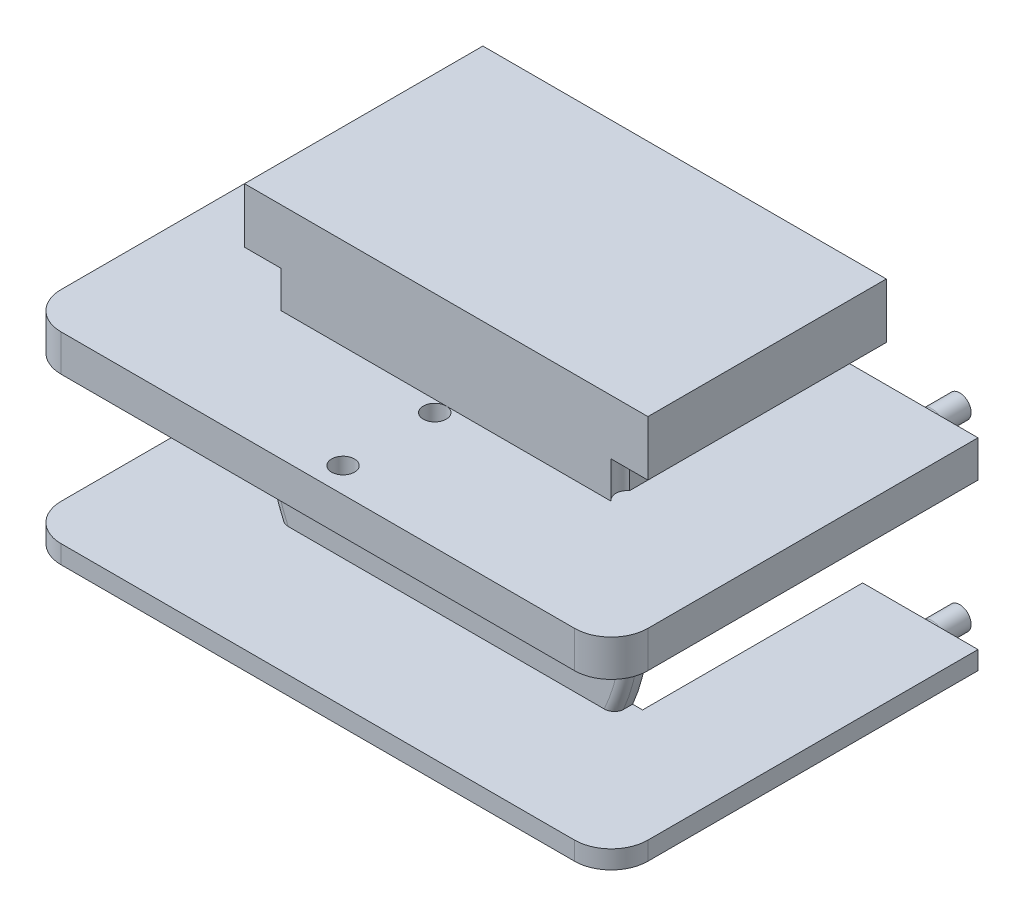
SolidWorks part; units mm, degrees
material "UNOBTANIUM"
ref_plane "Top Plane" through (0, 0, 0) normal (0, 0, 1) x (1, 0, 0)
ref_plane "Right Plane" through (0, 0, 0) normal (0, 1, 0) x (1, 0, 0)
ref_plane "Front Plane" through (0, 0, 0) normal (1, 0, 0) x (0, 0, -1)
ref_axis "x-axis" through (-17.6, 0, 0) along (1, 0, 0)
ref_axis "y-axis" through (0, -9.7375, 0) along (0, 1, 0)
ref_axis "z-axis" through (0, 0, 8.775) along (0, 0, -1)
sketch "Sketch1" plane through (0, 0, 0) normal (0, 0, 1) x (1, 0, 0)
  line L0 (-11, 6) -> (-11, 11)
  line L1 (-11, -6) -> (11, -6)
  line L2 (-11, -6) -> (-11, 6)
  line L3 (-11, 6) -> (11, 6) construction
  line L4 (11, -6) -> (11, 6)
  line L5 (-11, -6) -> (11, 6) construction
  line L6 (-11, 6) -> (11, -6) construction
  line L7 (-11, 11) -> (11, 11)
  line L8 (11, 11) -> (11, 6)
  circle A0 centre (0, 0) radius 9.25 construction
  point P0 (0, 0)
  dimension "D1" = 18.5
  dimension "D2" = 22
  dimension "D3" = 12
  dimension "D4" = 5
extrude "Boss-Extrude1" add sketch "Sketch1" along normal blind 1
sketch "Sketch2" plane through (0, 0, 0) normal (0, 0, -1) x (-1, 0, 0)
  circle A0 centre (0, 0) radius 1.475
  dimension "D1" = 2.95
extrude "Boss-Extrude2" add sketch "Sketch2" along normal blind 14
sketch "Sketch3" plane through (0, 0, 0) normal (0, 0, -1) x (-1, 0, 0)
  line L0 (11, -6) -> (-11, 6) construction
  circle A0 centre (0, 0) radius 1.8
  dimension "D1" = 3.6
extrude "Boss-Extrude3" add sketch "Sketch3" along normal blind 1
sketch "Sketch4" plane through (0, 0, 0) normal (0, 0, -1) x (-1, 0, 0)
  line L0 (11, -6) -> (-11, -6) construction
  line L1 (11, 11) -> (9, 11)
  line L2 (11, 11) -> (11, -6)
  line L3 (11, -6) -> (9, -6)
  line L4 (9, 11) -> (9, -6)
  line L5 (0, -6) -> (0, 11) construction
  line L7 (-9, 11) -> (-9, -6)
  line L8 (-11, -6) -> (-9, -6)
  line L9 (-11, 11) -> (-11, -6)
  line L10 (-11, 11) -> (-9, 11)
  line L11 (11, 11) -> (-11, 11) construction
  dimension "D1" = 2
extrude "Boss-Extrude4" add sketch "Sketch4" along normal blind 12
sketch "Sketch5" plane through (0, 0, 0) normal (0, 0, -1) x (-1, 0, 0)
  line L0 (-9, -6) -> (-9, 11) construction
  line L1 (9, 11) -> (-9, 11)
  line L2 (9, 11) -> (9, 9)
  line L3 (9, 9) -> (-9, 9)
  line L4 (-9, 11) -> (-9, 9)
  dimension "D1" = 2
extrude "Boss-Extrude5" add sketch "Sketch5" along normal up to surface (12 mm away) up to face at (-10, 2.5, -12)
sketch "Sketch6" plane through (11, 0, 0) normal (1, 0, 0) x (0, 0, -1)
  line L0 (-1, -6) -> (-1, 11) construction
  line L1 (12, -6) -> (-1, -6)
  line L2 (12, -6) -> (12, -4)
  line L3 (12, -4) -> (-1, -4)
  line L4 (-1, -6) -> (-1, -4)
  line L6 (12, 11) -> (12, -6) construction
  line L7 (-1, 6) -> (12, 6)
  line L8 (-1, 6) -> (-1, 4)
  line L9 (-1, 4) -> (12, 4)
  line L10 (12, 6) -> (12, 4)
  line L11 (5.5, 4) -> (5.5, -4) construction
  line L12 (0, 0) -> (5.5, 0) construction
  line L13 (0, -6) -> (0, 6) construction
  point P21 (5.5, 0)
  dimension "D1" = 2
extrude "Boss-Extrude6" add sketch "Sketch6" along normal blind 5
mirror "Mirror1" about plane through (0, 0, 0) normal (1, 0, 0) of "Boss-Extrude6"
sketch "Sketch7" plane through (0, 0, -12) normal (0, 0, -1) x (-1, 0, 0)
  line L0 (-9, -6) -> (-9, 9) construction
  line L1 (-9, 0) -> (-9, 9)
  line L2 (-9, 9) -> (0, 9)
  line L3 (-9, 0) -> (-9, -6)
  line L4 (-9, -6) -> (-6.7082, -6)
  line L5 (11, -6) -> (-11, -6) construction
  arc A0 (0, 9) -> (-6.7082, -6) centre (0, 0) ccw
  line M18 (-9, -6) -> (-9, 9)
  line M19 (-9, 9) -> (9, 9)
extrude "Boss-Extrude7" add sketch "Sketch7" against normal up to surface (12 mm away) contours A0 L4 M18 | A0 M19 M18 region at (8.3306, -4.5409, -12) region at (6.9897, 6.9897, -12) up to face at (1.8, 0, 0)
sketch "Sketch8" plane through (0, 0, -12) normal (0, 0, -1) x (-1, 0, 0)
  line L0 (-11, 4) -> (-9.1652, 4)
  line L1 (-11, 4) -> (-11, -4)
  line L2 (-11, -4) -> (-9.1652, -4)
  arc A1 (-9.1652, 4) -> (-9.1652, -4) centre (0, 0) ccw
  dimension "D1" = 10
extrude "Cut-Extrude1" cut sketch "Sketch8" against normal through all
sketch "Sketch9" plane through (0, 0, -12) normal (0, 0, -1) x (-1, 0, 0)
  line L0 (-16, -4) -> (-9.1652, -4) construction
  line L1 (-8.0623, 4) -> (-11, 4)
  line L2 (-8.0623, 4) -> (-8.0623, -4)
  line L3 (-8.0623, -4) -> (-11, -4)
  line L4 (-11, 4) -> (-11, -4)
  line L5 (-11, -6) -> (-11, 6) construction
  arc A0 (0, 9) -> (-6.7082, -6) centre (0, 0) ccw construction
  arc A1 (0, 9) -> (-6.7082, -6) centre (0, 0) ccw construction
extrude "Cut-Extrude2" cut sketch "Sketch9" against normal up to surface (12 mm away) up to face at (1.8, 0, 0)
mirror "Mirror2" about plane through (0, 0, 0) normal (1, 0, 0) of "Cut-Extrude2", "Cut-Extrude1", "Boss-Extrude7"
sketch "Sketch21" plane through (0, 0, -12) normal (0, 0, -1) x (-1, 0, 0)
  circle A0 centre (0, 0) radius 10.5
  circle A1 centre (0, 0) radius 9 construction
  circle A2 centre (0, 0) radius 1.8 construction
  circle A3 centre (0, 0) radius 1.8
  dimension "D1" = 1.5
extrude "Cut-Extrude11" cut sketch "Sketch21" against normal up to surface (12 mm away) up to face at (0, -0.7091, 0)
sketch "Sketch10" plane through (0, 0, 1) normal (0, 0, 1) x (1, 0, 0)
  line L0 (-16, -4) -> (-16, -6) construction
  line L1 (16, -6) -> (-16, -6)
  line L2 (16, -6) -> (16, -4)
  line L3 (16, -4) -> (-16, -4)
  line L4 (-16, -6) -> (-16, -4)
  line L5 (-16, -4) -> (-9.1652, -4) construction
  line L7 (-16, 6) -> (16, 6)
  line L8 (-16, 6) -> (-16, 4)
  line L9 (-16, 4) -> (16, 4)
  line L10 (16, 6) -> (16, 4)
extrude "Boss-Extrude8" add sketch "Sketch10" along normal blind 7
fillet "Fillet1" radius 0.5 2 edges at (10, 0, 1) (-10, 0, 1)
sketch "Sketch11" plane through (0, 0, -12) normal (0, 0, -1) x (-1, 0, 0)
  line L0 (-16, -5) -> (-13, -5) construction
  line L1 (-16, -6) -> (-16, -4) construction
  circle A0 centre (-13, -5) radius 0.625
  dimension "D1" = 1.25
  dimension "D2" = 3
extrude "Boss-Extrude9" add sketch "Sketch11" along normal blind 2
sketch "Sketch14" plane through (0, 0, -12) normal (0, 0, -1) x (-1, 0, 0)
  line L1 (11, 6) -> (9, 6)
  line L2 (11, 6) -> (11, 8)
  line L3 (11, 8) -> (9, 8)
  line L4 (9, 6) -> (9, 8)
  line L5 (-11, 6) -> (-9, 6)
  line L6 (-11, 6) -> (-11, 8)
  line L7 (-11, 8) -> (-9, 8)
  line L8 (-9, 6) -> (-9, 8)
  dimension "D1" = 18
  dimension "D2" = 2
extrude "Cut-Extrude5" cut sketch "Sketch14" against normal through all
sketch "Sketch12" plane through (0, 0, -12) normal (0, 0, -1) x (-1, 0, 0)
  line L0 (-16, -5) -> (-13, -5) construction
  line L1 (-16, -6) -> (-16, -4) construction
  line L3 (16, -5) -> (13, -5) construction
  line L4 (16, -6) -> (16, -4) construction
  circle A0 centre (13, -5) radius 0.675
  circle A1 centre (-13, -5) radius 0.625 construction
  circle A2 centre (-13, -5) radius 0.625 construction
  dimension "D1" = 1.35
  dimension "D2" = 1.25
extrude "Cut-Extrude3" cut sketch "Sketch12" against normal blind 2.5
sketch "Sketch16" plane through (0, 6, 0) normal (0, 1, 0) x (1, 0, 0)
  line L0 (-9, -1) -> (-9, 12) construction
  line L1 (-9, 0) -> (-9, -1)
  arc A1 (-9, 0) -> (-9, -1) centre (-9.375, -0.5) cw
  dimension "D1" = 0.25
  dimension "D2" = 1
extrude "Cut-Extrude6" cut sketch "Sketch16" along normal blind 2
mirror "Mirror3" about plane through (0, 0, 0) normal (0, 1, 0) of "Boss-Extrude9", "Cut-Extrude3"
mirror "Mirror4" about plane through (0, 0, 0) normal (1, 0, 0) of "Cut-Extrude6"
fillet "Fillet2" radius 0.5 2 edges at (12.375, 5, -12) (13.625, -5, -12)
fillet "Fillet3" radius 0.5 2 edges at (-13.675, 5, -12) (-13.675, -5, -12)
fillet "Fillet4" radius 2 4 edges at (16, -5, 8) (16, 5, 8) (-16, -5, 8) (-16, 5, 8)
sketch "Sketch17" plane through (0, -6, 0) normal (0, -1, 0) x (1, 0, 0)
  line L0 (-16, 6) -> (-16, -12) construction
  line L1 (-14, 8) -> (14, 8) construction
  line L2 (16, 6) -> (16, -12) construction
  line L3 (-16, 6) -> (-16, -12)
  line L4 (-14, 8) -> (14, 8)
  line L5 (16, 6) -> (16, -12)
  line L6 (14.5, 6) -> (14.5, -12)
  line L8 (-14, 6.5) -> (14, 6.5)
  line L9 (-14.5, 6) -> (-14.5, -12)
  line L10 (14.5, -12) -> (16, -12)
  line L11 (-14.5, -12) -> (-16, -12)
  arc A0 (-14, 8) -> (-16, 6) centre (-14, 6) ccw construction
  arc A1 (16, 6) -> (14, 8) centre (14, 6) ccw construction
  arc A2 (-14, 8) -> (-16, 6) centre (-14, 6) ccw
  arc A3 (16, 6) -> (14, 8) centre (14, 6) ccw
  arc A4 (14.5, 6) -> (14, 6.5) centre (14, 6) ccw
  arc A5 (-14, 6.5) -> (-14.5, 6) centre (-14, 6) ccw
  dimension "D1" = 1.5
extrude "Cut-Extrude7" cut sketch "Sketch17" against normal blind 1 and the other way through all
sketch "Sketch19" plane through (0, 6, 0) normal (0, 1, 0) x (1, 0, 0)
  line L0 (9, -1) -> (-9, -1) construction
  line L1 (0, -1.625) -> (0, -1) construction
  line L2 (9, -1) -> (-9, -1) construction
  circle A0 centre (0, -1.625) radius 0.625
  circle A1 centre (0, -6.625) radius 0.625
  point P4 (0, -1)
  dimension "D1" = 1.25
  dimension "D2" = 5
extrude "Cut-Extrude9" cut sketch "Sketch19" against normal up to surface (2 mm away) up to face at (0.0154, 4, -3.1999)
sketch "Sketch20" plane through (0, 0, -12) normal (0, 0, -1) x (-1, 0, 0)
  line L0 (-9, 8) -> (-11, 8) construction
  line L1 (-11, 11) -> (-9, 11)
  line L2 (-11, 11) -> (-11, 8)
  line L3 (-11, 8) -> (-9, 8)
  line L4 (-9, 11) -> (-9, 8)
  line L5 (11, 11) -> (-11, 11) construction
  line L6 (11, 8) -> (9, 8)
  line L7 (11, 8) -> (11, 11)
  line L8 (11, 11) -> (9, 11)
  line L9 (9, 8) -> (9, 11)
  dimension "D1" = 2
equation "\"D1@Sketch12\"=\"D2@Sketch12\"+.1"
